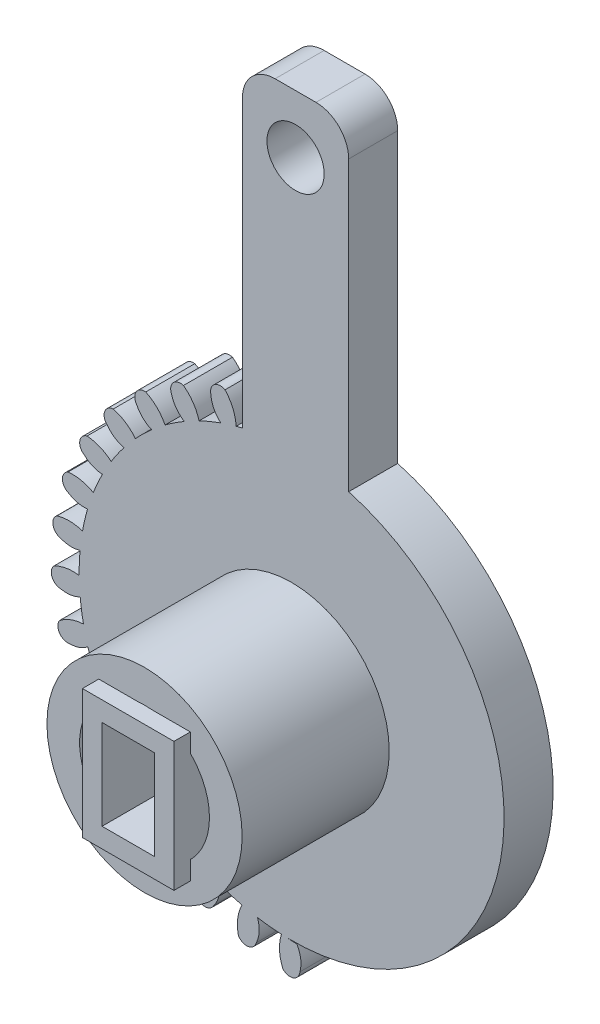
SolidWorks part; units mm, degrees
ref_plane "Front Plane" through (0, 0, 0) normal (0, 0, 1) x (1, 0, 0)
ref_plane "Top Plane" through (0, 0, 0) normal (0, 1, 0) x (1, 0, 0)
ref_plane "Right Plane" through (0, 0, 0) normal (1, 0, 0) x (0, 0, -1)
ref_plane "Plane1" through (0, 0, 5) normal (0, 0, 1) x (1, 0, 0)
ref_plane "Plane2" through (0, 0, 11) normal (0, 0, 1) x (1, 0, 0)
ref_plane "Plane3" through (0, 0, 3) normal (0, 0, 1) x (1, 0, 0)
sketch "Sketch1" plane through (0, 0, 5) normal (0, 0, 1) x (1, 0, 0)
  circle A0 centre (0, 20.9252) radius 3.9726
  circle A1 centre (0, 20.9252) radius 5
  dimension "D1" = 10
sketch "Sketch3" plane through (0, 0, 11) normal (0, 0, 1) x (1, 0, 0)
  line L0 (-3.9726, 20.9252) -> (15.3734, 20.9252) construction
  line L1 (0, 24.8978) -> (0, 8.7425) construction
  line L3 (-1.6, 23.6752) -> (1.6, 23.6752)
  line L4 (-1.6, 23.6752) -> (-1.6, 18.1752)
  line L5 (-1.6, 18.1752) -> (1.6, 18.1752)
  line L6 (1.6, 23.6752) -> (1.6, 18.1752)
  dimension "D1" = 3.2
  dimension "D2" = 5.5
  dimension "D3" = 1.6
  dimension "D4" = 2.75
extrude "Boss-Extrude1" add sketch "Sketch1" along normal blind 10 contours A0
shell "Shell1" thickness 2 removed face at (3.9726, 20.9252, 15) outward yes
extrude "Boss-Extrude2" add sketch "Sketch3" along normal blind 5 separate body
shell "Shell2" thickness 1.2 removed face at (0, 20.9252, 16) outward yes
sketch "Sketch7" plane through (0, 0, 3) normal (0, 0, -1) x (-1, 0, 0)
  line L0 (0, 14.9526) -> (0, 35.2199) construction
  line L1 (5.9726, 20.9252) -> (-26.894, 20.9252) construction
  circle A0 centre (0, 20.9252) radius 5.9726 construction
sketch "Sketch5" plane through (0, 0, 3) normal (0, 0, 1) x (1, 0, 0)
  line L1 (0, 14.9526) -> (0, 35.2199) construction
  line L2 (-5.9726, 20.9252) -> (26.894, 20.9252) construction
  circle A0 centre (0, 20.9252) radius 13
extrude "Boss-Extrude3" add sketch "Sketch5" along normal blind 3 contours A0
sketch "Sketch6" plane through (0, 0, 3) normal (0, 0, 1) x (1, 0, 0)
  line L1 (-3.01, 33.0817) -> (3.49, 33.0817)
  line L2 (-3.01, 33.0817) -> (-3.01, 53.0817)
  line L3 (-3.01, 53.0817) -> (3.49, 53.0817)
  line L4 (3.49, 33.0817) -> (3.49, 53.0817)
  dimension "D1" = 20
  dimension "D2" = 6.5
extrude "Boss-Extrude4" add sketch "Sketch6" along normal up to surface (3 mm away) up to face at (5.9726, 20.9252, 6)
sketch "Sketch8" plane through (0, 0, 3) normal (0, 0, 1) x (1, 0, 0)
  line L0 (-4.296, 33.1462) -> (-3.39, 33.4105)
  line L1 (0.24, 53.0817) -> (0.24, -3.388) construction
  line L2 (3.49, 53.0817) -> (-3.01, 53.0817) construction
  line L3 (13, 20.9252) -> (-7.0281, 20.9252) construction
  line L4 (-6.4797, 32.0955) -> (-5.6382, 32.5229)
  line L5 (-8.4311, 30.6587) -> (-7.6833, 31.2345)
  line L6 (-10.0829, 28.8855) -> (-9.4546, 29.5898)
  line L7 (-11.3779, 26.8373) -> (-10.8908, 27.6456)
  line L8 (-12.2715, 24.5847) -> (-11.9424, 25.4693)
  line L9 (-12.7326, 22.2057) -> (-12.573, 23.1358)
  line L10 (-12.7455, 19.7824) -> (-12.7607, 20.726)
  line L11 (-12.3095, 17.3986) -> (-12.4992, 18.3231)
  line L12 (-11.4399, 15.1367) -> (-11.7974, 16.0101)
  line L13 (-10.1667, 13.0748) -> (-10.6797, 13.867)
  line L14 (-8.5338, 11.2842) -> (-9.1845, 11.9678)
  line L15 (-6.5977, 9.8268) -> (-7.3637, 10.3781)
  line L16 (-4.4253, 8.753) -> (-5.2801, 9.1529)
  line L17 (-2.0916, 8.0998) -> (-3.0057, 8.3346)
  line L18 (0.3226, 7.8899) -> (-0.6192, 7.9514)
  arc A0 (-3.39, 33.4105) -> (-4.0758, 35.0663) centre (-5.9543, 33.3183) ccw
  arc A1 (-5.6382, 32.5229) -> (-6.6186, 34.0231) centre (-8.1411, 31.9576) ccw
  arc A2 (-4.0758, 35.0663) -> (-4.9399, 34.3825) centre (-4.3614, 34.5393) ccw
  arc A3 (-4.9399, 34.3825) -> (-4.296, 33.1462) centre (-3.1926, 34.5068) ccw
  arc A4 (-3.01, 33.572) -> (3.49, 33.448) centre (0, 20.9252) ccw construction
  arc A5 (-6.6186, 34.0231) -> (-7.3413, 33.1912) centre (-6.8018, 33.4524) ccw
  arc A6 (-7.3413, 33.1912) -> (-6.4797, 32.0955) centre (-5.6471, 33.6368) ccw
  arc A7 (-7.6833, 31.2345) -> (-8.9245, 32.5273) centre (-10.0383, 30.2157) ccw
  arc A8 (-8.9245, 32.5273) -> (-9.4806, 31.576) centre (-8.9988, 31.9325) ccw
  arc A9 (-9.4806, 31.576) -> (-8.4311, 30.6587) centre (-7.8982, 32.3274) ccw
  arc A10 (-9.4546, 29.5898) -> (-10.9136, 30.6305) centre (-11.5804, 28.1527) ccw
  arc A11 (-10.9136, 30.6305) -> (-11.2841, 29.5927) centre (-10.8765, 30.0323) ccw
  arc A12 (-11.2841, 29.5927) -> (-10.0829, 28.8855) centre (-9.8681, 30.6241) ccw
  arc A13 (-10.8908, 27.6456) -> (-12.5173, 28.3983) centre (-12.7139, 25.8399) ccw
  arc A14 (-12.5173, 28.3983) -> (-12.6892, 27.3099) centre (-12.3701, 27.8173) ccw
  arc A15 (-12.6892, 27.3099) -> (-11.3779, 26.8373) centre (-11.4887, 28.5855) ccw
  arc A16 (-11.9424, 25.4693) -> (-13.6801, 25.9079) centre (-13.3997, 23.3573) ccw
  arc A17 (-13.6801, 25.9079) -> (-13.6476, 24.8064) centre (-13.4279, 25.3641) ccw
  arc A18 (-13.6476, 24.8064) -> (-12.2715, 24.5847) centre (-12.7039, 26.2823) ccw
  arc A19 (-12.573, 23.1358) -> (-14.3618, 23.2453) centre (-13.6142, 20.7907) ccw
  arc A20 (-14.3618, 23.2453) -> (-14.126, 22.1688) centre (-14.0133, 22.7576) ccw
  arc A21 (-14.126, 22.1688) -> (-12.7326, 22.2057) centre (-13.4718, 23.7938) ccw
  arc A22 (-12.7607, 20.726) -> (-14.5389, 20.5025) centre (-13.3499, 18.2286) ccw
  arc A23 (-14.5389, 20.5025) -> (-14.1079, 19.4883) centre (-14.1062, 20.0877) ccw
  arc A24 (-14.1079, 19.4883) -> (-12.7455, 19.7824) centre (-13.7658, 21.2063) ccw
  arc A25 (-12.4992, 18.3231) -> (-14.2053, 17.7743) centre (-12.616, 15.7598) ccw
  arc A26 (-14.2053, 17.7743) -> (-13.5941, 16.8574) centre (-13.7033, 17.4468) ccw
  arc A27 (-13.5941, 16.8574) -> (-12.3095, 17.3986) centre (-13.5758, 18.609) ccw
  arc A28 (-11.7974, 16.0101) -> (-13.3725, 15.155) centre (-11.4377, 13.4695) ccw
  arc A29 (-13.3725, 15.155) -> (-12.6021, 14.3671) centre (-12.8185, 14.926) ccw
  arc A30 (-12.6021, 14.3671) -> (-11.4399, 15.1367) centre (-12.9084, 16.0918) ccw
  arc A31 (-10.6797, 13.867) -> (-12.0692, 12.7351) centre (-9.8559, 11.4368) ccw
  arc A32 (-12.0692, 12.7351) -> (-11.1663, 12.1034) centre (-11.4825, 12.6126) ccw
  arc A33 (-11.1663, 12.1034) -> (-10.1667, 13.0748) centre (-11.7865, 13.7417) ccw
  arc A34 (-9.1845, 11.9678) -> (-10.3406, 10.5982) centre (-7.9252, 9.7321) ccw
  arc A35 (-10.3406, 10.5982) -> (-9.3363, 10.1446) centre (-9.7413, 10.5865) ccw
  arc A36 (-9.3363, 10.1446) -> (-8.5338, 11.2842) centre (-10.2491, 11.6397) ccw
  arc A37 (-7.3637, 10.3781) -> (-8.2463, 8.8183) centre (-5.7123, 8.4142) ccw
  arc A38 (-8.2463, 8.8183) -> (-7.1754, 8.5583) centre (-7.6552, 8.9177) ccw
  arc A39 (-7.1754, 8.5583) -> (-6.5977, 9.8268) centre (-8.3491, 9.8587) ccw
  arc A40 (-5.2801, 9.1529) -> (-5.8587, 7.4567) centre (-3.2937, 7.5286) ccw
  arc A41 (-5.8587, 7.4567) -> (-4.7582, 7.3995) centre (-5.2962, 7.6638) ccw
  arc A42 (-4.7582, 7.3995) -> (-4.4253, 8.753) centre (-6.1524, 8.4601) ccw
  arc A43 (-3.0057, 8.3346) -> (-3.2603, 6.5606) centre (-0.753, 7.106) ccw
  arc A44 (-3.2603, 6.5606) -> (-2.1683, 6.7081) centre (-2.7459, 6.8682) ccw
  arc A45 (-2.1683, 6.7081) -> (-2.0916, 8.0998) centre (-3.7347, 7.4923) ccw
  arc A46 (-0.6192, 7.9514) -> (-0.541, 6.1609) centre (1.822, 7.161) ccw
  arc A47 (-0.541, 6.1609) -> (0.5049, 6.508) centre (-0.0924, 6.5585) ccw
  arc A48 (0.5049, 6.508) -> (0.3226, 7.8899) centre (-1.1796, 6.9887) ccw
  point P26 (0.24, 20.9252)
  point P153 (0.24, 20.9252)
  dimension "D1" = 16
extrude "Boss-Extrude5" add sketch "Sketch8" along normal up to surface (3 mm away) up to face at (3.9726, 20.9252, 6)
sketch "Sketch9" plane through (0, 0, 3) normal (0, 0, -1) x (-1, 0, 0)
  line L0 (-0.24, 53.0817) -> (-0.24, 49.0919) construction
  line L1 (-3.49, 53.0817) -> (3.01, 53.0817) construction
  circle A0 centre (-0.24, 49.5317) radius 1.75
  dimension "D1" = 3.55
extrude "Cut-Extrude1" cut sketch "Sketch9" against normal up to surface (3 mm away) up to face at (3.9726, 20.9252, 6)
fillet "Fillet1" radius 2 2 edges at (3.49, 53.0817, 4.5) (-3.01, 53.0817, 4.5)
